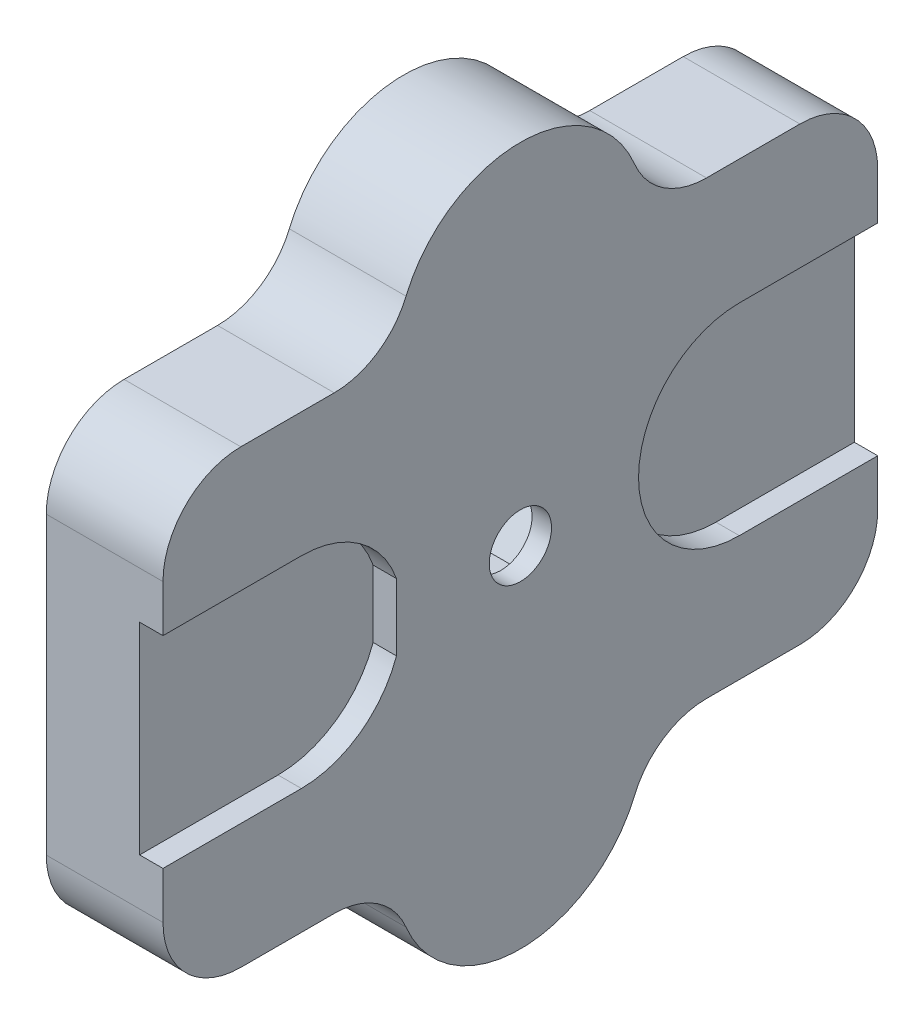
SolidWorks part; units mm, degrees
material "ABS"
ref_plane "Front Plane" through (0, 0, 0) normal (1, 0, 0) x (0, 1, 0)
ref_plane "Top Plane" through (0, 0, 0) normal (0, 0, 1) x (0, 1, 0)
ref_plane "Right Plane" through (0, 0, 0) normal (0, 1, 0) x (-1, 0, 0)
sketch "Sketch1" plane through (0, 0, 0) normal (1, 0, 0) x (0, 1, 0)
  line L0 (-28.9545, 0) -> (33.8464, 0) construction
  line L3 (-28.9686, 19.054) -> (-28.9686, -12.7893) construction
  line L4 (0, 49.054) -> (0, -56.7378) construction
  line L6 (-28.9686, -12.7893) -> (28.9686, -12.7893)
  line L7 (44.5791, 0) -> (-44.5791, 0) construction
  line L9 (18.9686, 49.054) -> (-18.9686, 49.054)
  line L12 (-28.9686, 39.054) -> (-28.9686, 27.0474)
  line L13 (28.9686, 19.054) -> (28.9686, -12.7893) construction
  line L14 (28.9686, 39.054) -> (28.9686, 27.0474)
  line L15 (-28.9686, 19.054) -> (28.9686, 19.054) construction
  line L16 (-28.9686, 19.054) -> (28.9686, 19.054) construction
  arc A3 (-35.1108, 17.8215) -> (-28.9686, -12.7893) centre (-28.9686, 3.1323) ccw
  arc A4 (-18.9686, 49.054) -> (-28.9686, 39.054) centre (-18.9686, 39.054) ccw
  arc A5 (-35.1108, 17.8215) -> (-28.9686, 27.0474) centre (-38.9686, 27.0474) ccw
  arc A6 (35.1108, 17.8215) -> (28.9686, 27.0474) centre (38.9686, 27.0474) cw
  arc A7 (18.9686, 49.054) -> (28.9686, 39.054) centre (18.9686, 39.054) cw
  arc A8 (35.1108, 17.8215) -> (28.9686, -12.7893) centre (28.9686, 3.1323) cw
  point P20 (0, 0)
  dimension "D1" = 10
  dimension "D2" = 10
extrude "Boss-Extrude3" add sketch "Sketch1" along normal blind 15
sketch "Sketch3" plane through (15, 0, 0) normal (1, 0, 0) x (0, 1, 0)
  line L0 (-44.8903, 3.1323) -> (44.8903, 3.1323) construction
  line L2 (-28.9686, -12.7893) -> (28.9686, -12.7893) construction
  line L3 (0, -12.7893) -> (0, 49.054) construction
  line L4 (18.9686, 49.054) -> (-18.9686, 49.054) construction
  arc A3 (-35.1108, 17.8215) -> (-28.9686, -12.7893) centre (-28.9686, 3.1323) ccw construction
  arc A4 (28.9686, -12.7893) -> (35.1108, 17.8215) centre (28.9686, 3.1323) ccw construction
  circle A5 centre (0, 3.1323) radius 4
extrude "Cut-Extrude3" cut sketch "Sketch3" against normal blind 14.0462
sketch "Sketch4" plane through (15, 0, 0) normal (1, 0, 0) x (0, 1, 0)
  line L0 (-12.95, 49.054) -> (-12.95, 31.2677)
  line L4 (18.9686, 49.054) -> (-18.9686, 49.054) construction
  line L6 (0, 7.1323) -> (0, 31.2677) construction
  line L7 (12.95, 31.2677) -> (12.95, 49.054)
  line L8 (-12.95, 49.054) -> (12.95, 49.054)
  circle A1 centre (0, 3.1323) radius 4 construction
  circle A2 centre (0, 31.2677) radius 12.95 construction
  arc A3 (-12.95, 31.2677) -> (12.95, 31.2677) centre (0, 31.2677) ccw
extrude "Cut-Extrude4" cut sketch "Sketch4" against normal blind 3
sketch "Sketch5" plane through (15, 0, 0) normal (1, 0, 0) x (0, 1, 0)
  line L0 (-2.9918, 7.8662) -> (2.9918, -1.6015) construction
  line L1 (5.4662, 6.587) -> (-0.2587, 9.5935)
  line L2 (-0.2587, 9.5935) -> (-5.7249, 6.1388)
  line L3 (-5.7249, 6.1388) -> (-5.4662, -0.3223)
  line L4 (-5.4662, -0.3223) -> (0.2587, -3.3288)
  line L5 (0.2587, -3.3288) -> (5.7249, 0.1258)
  line L6 (5.7249, 0.1258) -> (5.4662, 6.587)
  circle A0 centre (0, 3.1323) radius 5.6 construction
  dimension "D1" = 11.2
extrude "Cut-Extrude5" cut sketch "Sketch5" along direction (1, 0, 0) on the side against the normal mid plane 25 from surface starting at face at (0, 0, 23.7628)
sketch "Sketch6" plane through (15, 0, 0) normal (1, 0, 0) x (0, 1, 0)
  line L0 (-28.9686, 3.1323) -> (28.9686, 3.1323) construction
ref_plane "Plane1" through (0, 0, 3.1323) normal (0, 0, 1) x (0, 1, 0)
mirror "Mirror1" about plane through (0, 0, 3.1323) normal (0, 0, 1) of "Boss-Extrude3", "Cut-Extrude3", "Cut-Extrude4", "Cut-Extrude5"
